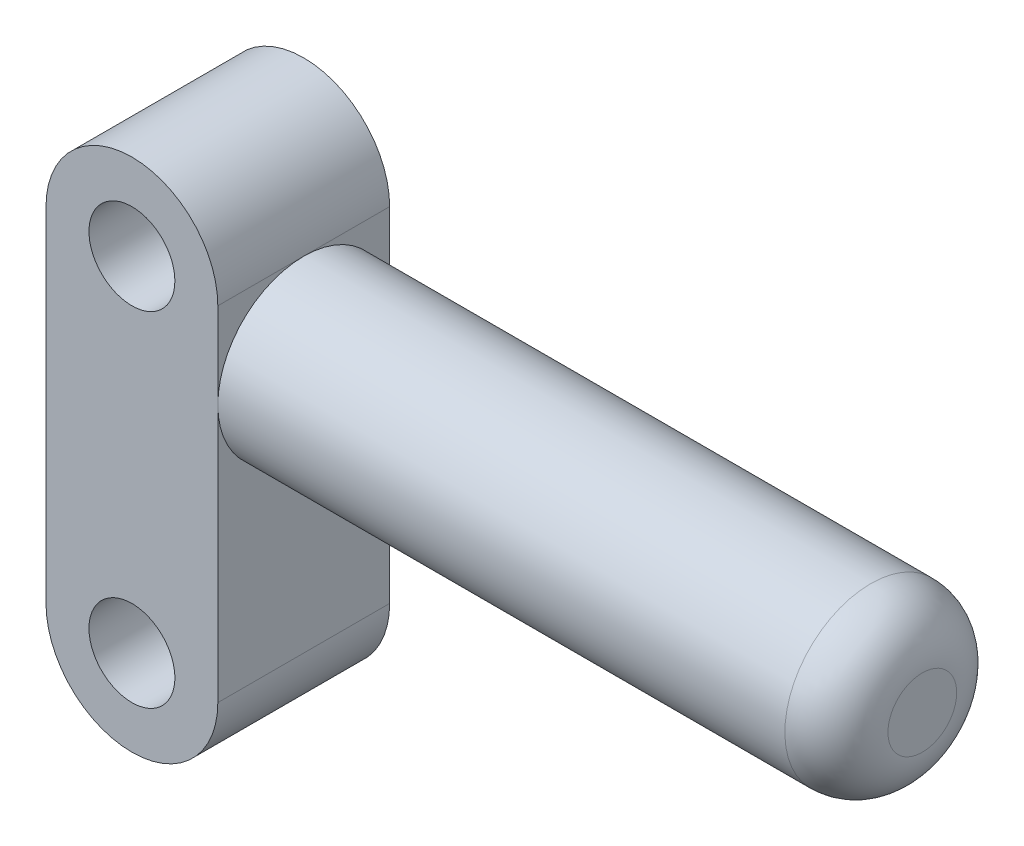
SolidWorks part; units mm, degrees
ref_plane "Plan de face" through (0, 0, 0) normal (0, 0, 1) x (1, 0, 0)
ref_plane "Plan de dessus" through (0, 0, 0) normal (0, 1, 0) x (1, 0, 0)
ref_plane "Plan de droite" through (0, 0, 0) normal (1, 0, 0) x (0, 0, -1)
other "Centre de masse"
sketch "Esquisse1" plane through (0, 0, 0) normal (0, 0, 1) x (1, 0, 0)
  line L0 (0, 10) -> (0, -10) construction
  line L1 (5, 10) -> (5, -10)
  line L2 (-5, 10) -> (-5, -10)
  line L3 (0, 0) -> (16.4339, 0) construction
  arc A0 (5, 10) -> (-5, 10) centre (0, 10) ccw
  arc A1 (-5, -10) -> (5, -10) centre (0, -10) ccw
  circle A2 centre (0, 10) radius 2.5
  circle A3 centre (0, -10) radius 2.5
  point P3 (0, 0)
  dimension "D3" = 5
  dimension "D2" = 10
extrude "Boss.-Extru.1" add sketch "Esquisse1" along normal mid plane 10
sketch "Esquisse2" plane through (5, 0, 0) normal (1, 0, 0) x (0, 0, -1)
  line L0 (0, 11.352) -> (0, 0) construction
  line L1 (0, 0) -> (4.254, 0) construction
  circle A0 centre (0, 5) radius 5
  dimension "D1" = 10
extrude "Boss.-Extru.2" add sketch "Esquisse2" along normal blind 36 contours A0
fillet "Congé1" radius 3 1 edges at (41, 10, 0)
ref_axis "Axe1" through (0, 10, 5) along (0, 0, -1)
ref_point "Point1"
equation "\"e\"= 0.01m"
equation "\"d\"= 0.05"
equation "\"l\"= 0.01"
equation "\"D2@Esquisse1\"=\"l\""
equation "\"D1@Boss.-Extru.1\"=\"e\""
equation "\"Ddoigt\"= 0.01m"
equation "\"D1@Esquisse2\"=\"Ddoigt\""
equation "\"Ldoigt\"= 0.036m"
equation "\"D1@Boss.-Extru.2\"=\"Ldoigt\""
equation "\"D1@Congé1\"=\"Ldoigt\"/12m"
